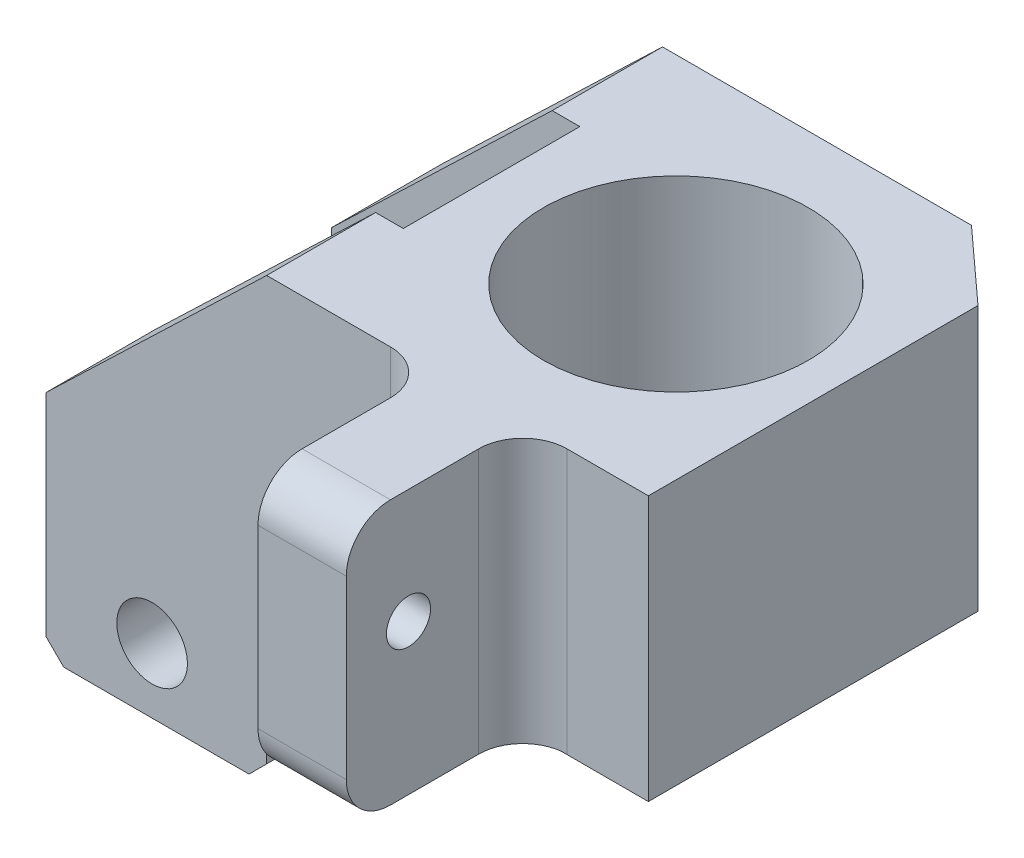
SolidWorks part; units mm, degrees
ref_plane "Спереди" through (0, 0, 0) normal (0, 0, 1) x (1, 0, 0)
ref_plane "Сверху" through (0, 0, 0) normal (0, 1, 0) x (1, 0, 0)
ref_plane "Справа" through (0, 0, 0) normal (1, 0, 0) x (0, 0, -1)
sketch "Эскиз1" plane through (0, 0, 0) normal (0, 1, 0) x (1, 0, 0)
  line L0 (-8.5273, 0) -> (45.8432, 0) construction
  line L1 (-24.0191, 22.5) -> (10.9809, 22.5)
  line L2 (-24.0191, 22.5) -> (-24.0191, -22.3428)
  line L3 (-24.0191, -22.3428) -> (19.2235, -22.3428)
  line L4 (19.2235, 15) -> (19.2235, -22.3428)
  line L8 (10.9809, 22.5) -> (19.2235, 15)
extrude "Вытянуть1" add sketch "Эскиз1" along normal blind 30
sketch "Эскиз2" plane through (0, 30, 0) normal (0, 1, 0) x (1, 0, 0)
  circle A0 centre (0, 0) radius 15
extrude "Вытянуть2" cut sketch "Эскиз2" against normal through all
sketch "Эскиз6" plane through (0, 0, -22.5) normal (0, 0, -1) x (-1, 0, 0)
  line L0 (24.0191, -19.9275) -> (24.0191, 30)
  line L2 (49.0191, -19.9275) -> (49.0191, 6.0126)
  line L3 (49.0191, -19.9275) -> (24.0191, -19.9275)
  line L4 (24.0191, 30) -> (49.0191, 6.0126)
extrude "Вытянуть3" add sketch "Эскиз6" against normal up to vertex (44.8428 mm away) up to point (-24.0191, 30, 22.3428)
sketch "Эскиз3" plane through (0, 30, 0) normal (0, 1, 0) x (1, 0, 0)
  line L0 (-38.6818, 0) -> (-47.6939, 0) construction
  line L3 (-65.5391, 10) -> (-20.8824, 10)
  line L4 (-65.5391, 10) -> (-65.5391, -10)
  line L5 (-65.5391, -10) -> (-20.8824, -10)
  line L6 (-20.8824, 10) -> (-20.8824, -10)
  line L7 (-65.5391, 10) -> (-20.8824, -10) construction
  line L8 (-65.5391, -10) -> (-20.8824, 10) construction
  point P1 (-43.2108, 0)
extrude "Вырез-Вытянуть1" cut sketch "Эскиз3" against normal blind 130 from offset 70
sketch "Эскиз7" plane through (0, 0, -22.5) normal (0, 0, -1) x (-1, 0, 0)
  circle A0 centre (37, -12.5783) radius 4
extrude "Вырез-Вытянуть2" cut sketch "Эскиз7" against normal through all
fillet "Скругление1" radius 5 1 edges
chamfer "Фаска5" distance 2 angle 45 4 edges at (-24.0191, -19.9275, -16.25) (-24.0191, -19.9275, 16.1714) (-49.0191, -19.9275, -16.25) (-49.0191, -19.9275, 16.1714)
sketch "Эскиз8" plane through (0, 0, 22.3428) normal (0, 0, 1) x (1, 0, 0)
  line L0 (0, 27.3471) -> (0, -2.3314) construction
  line L1 (-24.0191, 30) -> (19.2235, 30) construction
  line L2 (5, 0.0427) -> (-5, 0.0427)
  line L3 (5, 0.0427) -> (5, 30)
  line L4 (5, 30) -> (-5, 30)
  line L5 (-5, 0.0427) -> (-5, 30)
  line L6 (5, 0.0427) -> (-5, 30) construction
  line L7 (5, 30) -> (-5, 0.0427) construction
  line L9 (17.5635, 0) -> (29.9199, 0) construction
  line L10 (17.4362, 30) -> (26.6717, 30) construction
  point P1 (0, 15.0213)
  dimension "D1" = 5
extrude "Вытянуть4" add sketch "Эскиз8" along normal blind 20
fillet "Скругление2" radius 5 4 edges at (0, 30, 42.3428) (0, 0.0427, 42.3428)
sketch "Эскиз10" plane through (5, 0, 0) normal (1, 0, 0) x (0, 0, -1)
  circle A0 centre (-35.2968, 17.0527) radius 2.5
extrude "Вырез-Вытянуть3" cut sketch "Эскиз10" against normal through all
